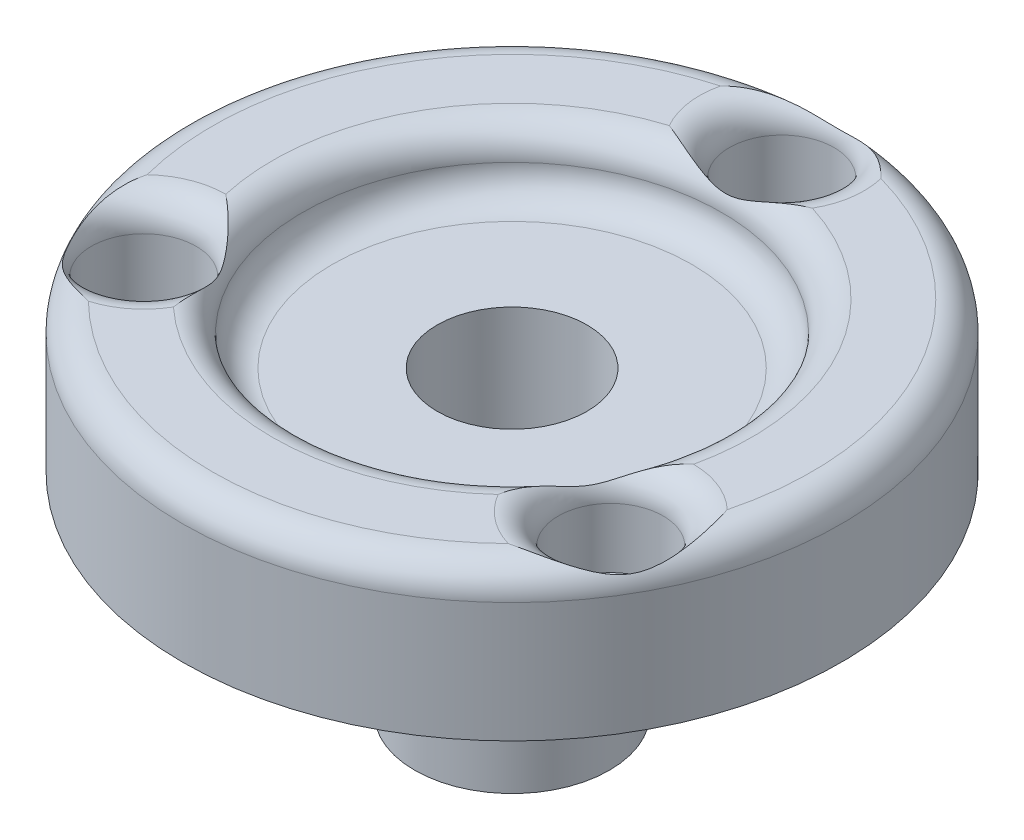
SolidWorks part; units mm, degrees
ref_plane "Front" through (0, 0, 0) normal (0, 0, 1) x (1, 0, 0)
ref_plane "Top" through (0, 0, 0) normal (0, 1, 0) x (1, 0, 0)
ref_plane "Right" through (0, 0, 0) normal (1, 0, 0) x (0, 0, -1)
sketch "Sketch1" plane through (0, 0, 0) normal (0, 1, 0) x (1, 0, 0)
  circle A0 centre (0, 0) radius 11
  dimension "D1" = 22
extrude "Boss-Extrude1" add sketch "Sketch1" along normal blind 5
sketch "Sketch2" plane through (0, 5, 0) normal (0, 1, 0) x (1, 0, 0)
  circle A0 centre (0, 9) radius 1.75
  circle A1 centre (7.7942, -4.5) radius 1.75
  circle A2 centre (-7.7942, -4.5) radius 1.75
  point P10 (0, 0)
  dimension "D1" = 3.5
  dimension "D2" = 9
  dimension "D3" = 3
extrude "Cut-Extrude1" cut sketch "Sketch2" against normal blind 3
sketch "Sketch3" plane through (0, 5, 0) normal (0, 1, 0) x (1, 0, 0)
  circle A0 centre (0, 0) radius 7
  dimension "D1" = 14
extrude "Cut-Extrude2" cut sketch "Sketch3" against normal blind 2
sketch "Sketch4" plane through (0, 0, 0) normal (0, -1, 0) x (1, 0, 0)
  circle A0 centre (0, 0) radius 3.25
  dimension "D1" = 6.5
extrude "Boss-Extrude3" add sketch "Sketch4" along normal blind 7
sketch "Sketch5" plane through (0, -7, 0) normal (0, -1, 0) x (1, 0, 0)
  circle A0 centre (0, 0) radius 2.5
  dimension "D1" = 5
extrude "Cut-Extrude3" cut sketch "Sketch5" against normal blind 15
fillet "Fillet3" radius 1 6 edges at (0, 3, 7) (0, 5, 11) (0, 5, -7.25) (7.7942, 5, 6.25) (-7.7942, 5, 6.25) (0, 5, 7)
